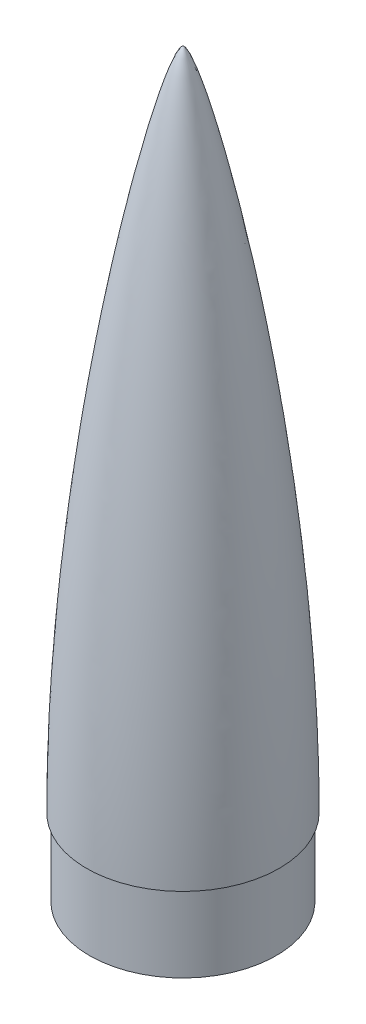
SolidWorks part; units mm, degrees
material "Plástico personalizado (1)"
ref_plane "Plano frontal" through (0, 0, 0) normal (0, 0, 1) x (1, 0, 0)
ref_plane "Plano superior" through (0, 0, 0) normal (0, 1, 0) x (1, 0, 0)
ref_plane "Plano direito" through (0, 0, 0) normal (1, 0, 0) x (0, 0, -1)
sketch "Esboço1" plane through (0, 0, 0) normal (0, 0, 1) x (1, 0, 0)
  line L0 (0, 0) -> (0, 250) construction
  line L3 (32.5, 115.6799) -> (32.5, -65.2833) construction
  line L4 (-61.4853, 250) -> (61.4853, 250) construction
  line L5 (0, 0) -> (0, 250)
  line L6 (0, 0) -> (31.5, 0)
  line L7 (31.5, 0) -> (31.5, 26)
  line L8 (31.5, 26) -> (32.5, 26)
  spline S0 degree 3 poles (32.5, 26) (32.5, 136) (5, 250) (0, 250) knots 0 0 0 0 1 1 1 1
  dimension "D4" = 15
  dimension "D5" = 330
  dimension "D1" = 250
  dimension "D2" = 31.5
  dimension "D3" = 1
  dimension "D6" = 26
revolve "Revolução1" add sketch "Esboço1" angle 360 about L5
shell "Casca3" thickness 1 removed face at (0, 0, -31.5)
